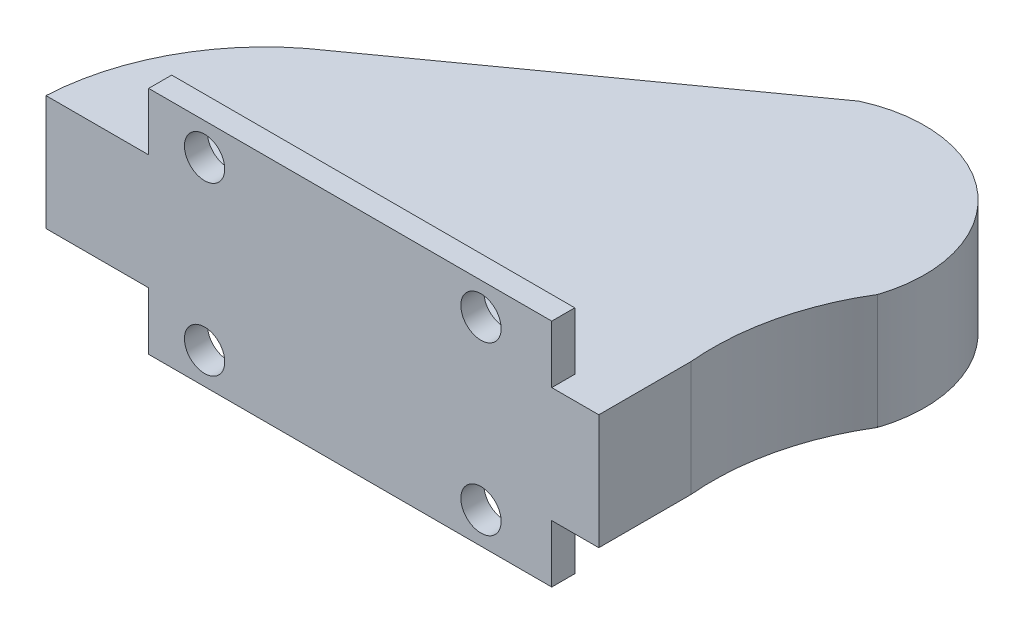
SolidWorks part; units mm, degrees
ref_plane "Front Plane" through (0, 0, 0) normal (0, 0, 1) x (1, 0, 0)
ref_plane "Top Plane" through (0, 0, 0) normal (0, 1, 0) x (1, 0, 0)
ref_plane "Right Plane" through (0, 0, 0) normal (1, 0, 0) x (0, 0, -1)
sketch "Sketch1" plane through (0, 0, 0) normal (0, 1, 0) x (1, 0, 0)
  line L0 (0, 0) -> (48, 0)
  line L1 (8.896, 15.667) -> (35.7221, 34.8857)
  line L2 (48, 0) -> (48, 8)
  arc A0 (0, 0) -> (8.896, 15.667) centre (19.9919, -0.9926) cw
  arc A1 (35.7221, 34.8857) -> (51.0575, 21.1506) centre (40.3853, 24.6636) cw
  arc A4 (48, 8) -> (51.0575, 21.1506) centre (69.3594, 9.9647) cw
  dimension "D1" = 48
  dimension "D2" = 33
extrude "Boss-Extrude1" add sketch "Sketch1" along normal blind 10
sketch "Sketch2" plane through (0, 0, 0) normal (0, 0, 1) x (1, 0, 0)
  line L0 (35.7221, 0) -> (51.6208, 0) construction
  line L1 (0, 5) -> (-11.7674, 5) construction
  line L2 (8.913, -5) -> (43.913, -5)
  line L3 (8.913, -5) -> (8.913, 0)
  line L4 (8.913, 0) -> (43.913, 0)
  line L5 (43.913, -5) -> (43.913, 0)
  line L6 (0, 10) -> (0, 0) construction
  line L7 (8.913, 10) -> (43.913, 10)
  line L8 (43.913, 15) -> (43.913, 10)
  line L9 (8.913, 15) -> (43.913, 15)
  line L10 (8.913, 15) -> (8.913, 10)
  dimension "D1" = 35
  dimension "D2" = 5
extrude "Boss-Extrude2" add sketch "Sketch2" against normal blind 2
sketch "Sketch3" plane through (0, 0, -2) normal (0, 0, -1) x (-1, 0, 0)
  circle A0 centre (-13.7694, -2.2635) radius 1.75
  circle A1 centre (-37.7694, -2.2635) radius 1.75
  circle A2 centre (-37.7694, 12.2365) radius 1.75
  circle A3 centre (-13.7694, 12.2365) radius 1.75
  dimension "D1" = 2
  dimension "D2" = 2
extrude "Cut-Extrude1" cut sketch "Sketch3" against normal blind 2
